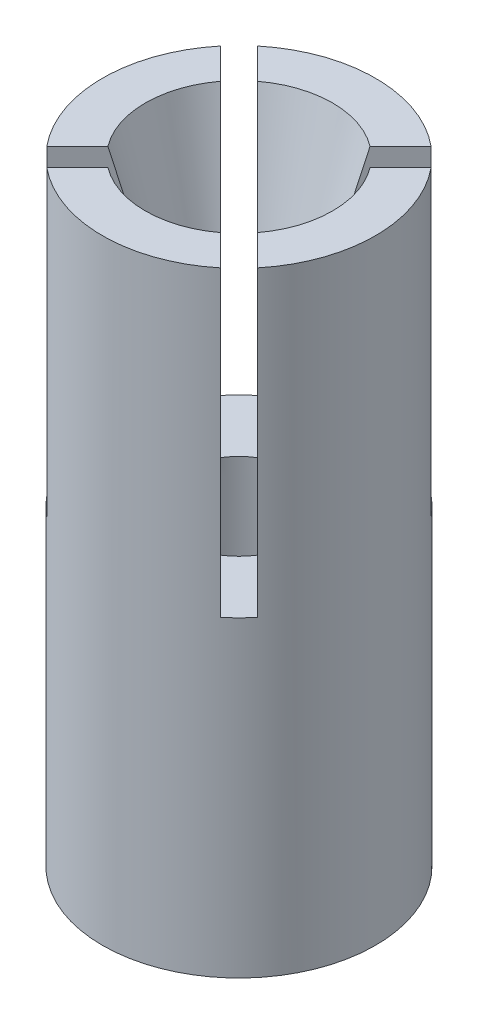
SolidWorks part; units mm, degrees
ref_plane "Front Plane" through (0, 0, 0) normal (0, 0, 1) x (1, 0, 0)
ref_plane "Top Plane" through (0, 0, 0) normal (0, 1, 0) x (1, 0, 0)
ref_plane "Right Plane" through (0, 0, 0) normal (1, 0, 0) x (0, 0, -1)
sketch "Sketch1" plane through (0, 0, 0) normal (0, 1, 0) x (1, 0, 0)
  circle A0 centre (0, 0) radius 16.6687
  dimension "D1" = 33.3375
extrude "Boss-Extrude1" add sketch "Sketch1" along normal blind 12.7 contours A0
sketch "Sketch2" plane through (0, 12.7, 0) normal (0, 1, 0) x (1, 0, 0)
  circle A0 centre (0, 0) radius 16.6687
  circle A1 centre (0, 0) radius 3.9688
  circle A2 centre (0, 0) radius 16.6687 construction
  dimension "D2" = 12.7
extrude "Boss-Extrude2" add sketch "Sketch2" along normal blind 62.357
ref_axis "Axis1" through (0, 75.057, 0) along (0, -1, 0)
ref_plane "Plane1" through (0, 0, 0) normal (-0.7071, 0, 0.7071) x (0, -1, 0)
ref_plane "Plane2" through (0, 57.15, 0) normal (0, 1, 0) x (1, 0, 0)
ref_plane "Plane3" through (0, 75.057, 0) normal (0, 1, 0) x (1, 0, 0)
sketch "Sketch7" plane through (0, 0, 0) normal (0, -1, 0) x (1, 0, 0)
  circle A0 centre (0, 0) radius 7.0714
  dimension "D1" = 14.1427
extrude "Cut-Extrude1" cut sketch "Sketch7" against normal blind 25.4
sketch "Sketch12" plane through (0, 57.15, 0) normal (0, 1, 0) x (1, 0, 0)
  circle A0 centre (0, 0) radius 14.2875
  dimension "D1" = 28.575
extrude "Boss-Extrude7" add sketch "Sketch12" along normal up to surface (17.907 mm away) contours A0 up to plane "Plane3"
sketch "Sketch10" plane through (0, 75.057, 0) normal (0, 1, 0) x (1, 0, 0)
  circle A0 centre (0, 0) radius 11.43
  dimension "D1" = 22.86
sketch "Sketch11" plane through (0, 57.15, 0) normal (0, 1, 0) x (1, 0, 0)
  circle A0 centre (0, 0) radius 6.6675
  dimension "D1" = 13.335
loft "Cut-Loft2" cut profiles "Sketch11", "Sketch10" connector at (-3.5336, 57.15, -5.6541) connector at (-6.811, 75.057, -9.1791)
sketch "Sketch9" plane through (0, 0, 0) normal (-0.7071, 0, 0.7071) x (0, -1, 0)
  line L7 (-38.1, -1.5875) -> (-190.5, -1.5875)
  line L8 (-38.1, -1.5875) -> (-38.1, 1.5875)
  line L9 (-38.1, 1.5875) -> (-190.5, 1.5875)
  line L10 (-190.5, -1.5875) -> (-190.5, 1.5875)
  line L11 (-38.1, -1.5875) -> (-190.5, 1.5875) construction
  line L12 (-38.1, 1.5875) -> (-190.5, -1.5875) construction
  line L15 (-38.1, -0.8001) -> (-38.1, 0.8001)
  line L18 (-75.057, 0) -> (-12.7, 0) construction
  point P4 (-34.925, 0)
  point P9 (-114.3, 0)
  point P16 (-9.5275, 0)
  dimension "D1" = 3.175
  dimension "D2" = 38.1
  dimension "D5" = 152.4
extrude "Cut-Extrude2" cut sketch "Sketch9" against normal up to next contours L7 L10 L9 L8
pattern_circular "CirPattern2" count 4 over 360 about axis through (0, 0, 0) along (0, 1, 0) of "Cut-Extrude2"
sketch "Sketch16" plane through (0, 25.4, 0) normal (0, -1, 0) x (1, 0, 0)
  circle A0 centre (0, 0) radius 8.001
  dimension "D1" = 16.002
loft "Cut-Loft3" cut profiles "Sketch16", "Sketch11<3>" connector at (-7.2713, 25.4, 3.3383) connector at (-6.0559, 57.15, 2.7895)
sketch "Sketch11<3>" plane through (0, 57.15, 0) normal (0, 1, 0) x (1, 0, 0) same geometry as "Sketch11"
thread "Thread1" pitch 1.4111 method cut profile "Thread Profile1" start angle 0, offset 0, length 0, pitch 1.4111, diameter 14.1427
ref_plane "Plane4" through (-7.0714, 25.4, 0) normal (0, 0, 1) x (-1, 0, 0)
sketch "Thread Profile1" plane through (-7.0714, 25.4, 0) normal (0, 0, 1) x (-1, 0, 0)
  line L0 (0, 0) -> (0, 1.4111) construction
  line L1 (0, 0) -> (0.7638, 0.441)
  line L2 (0.7638, 0.441) -> (0.7638, 0.6174)
  line L3 (0.7638, 0.6174) -> (0, 1.0583)
  line L4 (0.7638, 0.5292) -> (0, 0.5292) construction
  line L11 (0, 0) -> (0, 1.0583)
  point P2 (0, 0)
  dimension "Pitch" = 1.4111
  dimension "Profile_Angle" = 60
  dimension "Profile_Land" = 0.1764
  dimension "Profile_Height" = 0.7638
sketch "Sketch20" plane through (0, 0, 0) normal (0, -1, 0) x (1, 0, 0)
  circle A0 centre (0, 0) radius 8.001
  dimension "D1" = 16.002
extrude "Cut-Extrude3" cut sketch "Sketch20" against normal blind 2.54
